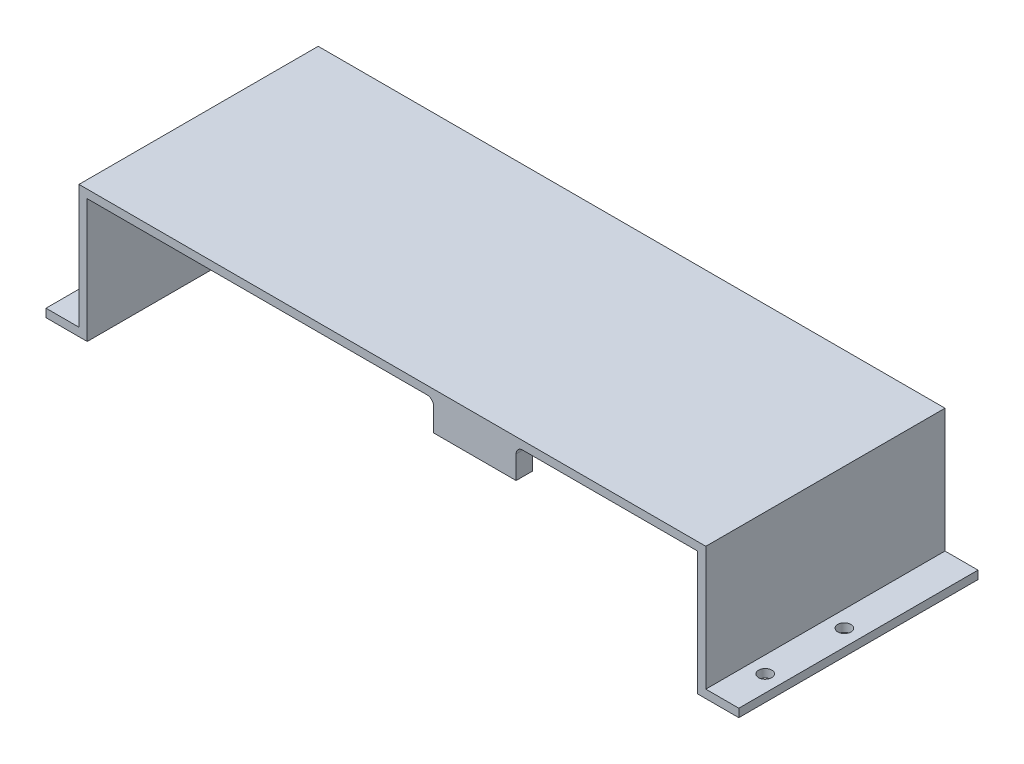
SolidWorks part; units mm, degrees
other "Markup1"
sketch "Sketch8" plane through (104.775, 3.175, 31.75) normal (0.0545, 0.0227, 0.9983) x (-0.9792, -0.1942, 0.0579)
ref_plane "Front Plane" through (0, 0, 0) normal (0, 0, 1) x (1, 0, 0)
ref_plane "Top Plane" through (0, 0, 0) normal (0, 1, 0) x (1, 0, 0)
ref_plane "Right Plane" through (0, 0, 0) normal (1, 0, 0) x (0, 0, -1)
sketch "Sketch1" plane through (0, 0, 0) normal (0, 1, 0) x (1, 0, 0)
  line L1 (-117.475, 46.0375) -> (117.475, 46.0375)
  line L2 (-117.475, 46.0375) -> (-117.475, -46.0375)
  line L3 (-117.475, -46.0375) -> (117.475, -46.0375)
  line L4 (117.475, 46.0375) -> (117.475, -46.0375)
  line L5 (-117.475, 46.0375) -> (117.475, -46.0375) construction
  line L6 (-117.475, -46.0375) -> (117.475, 46.0375) construction
  point P0 (0, 0)
  dimension "D1" = 234.95
  dimension "D2" = 92.075
extrude "Boss-Extrude1" add sketch "Sketch1" along normal blind 3.175
sketch "Sketch3" plane through (0, 3.175, 0) normal (0, 1, 0) x (1, 0, 0)
  line L0 (-117.475, -46.0375) -> (117.475, -46.0375) construction
  line L1 (-117.475, 46.0375) -> (-120.65, 46.0375)
  line L2 (-117.475, 46.0375) -> (-117.475, -46.0375)
  line L3 (-117.475, -46.0375) -> (-120.65, -46.0375)
  line L4 (-120.65, 46.0375) -> (-120.65, -46.0375)
  line L5 (0, -55) -> (0, 55) construction
  line L6 (117.475, -46.0375) -> (120.65, -46.0375)
  line L7 (120.65, 46.0375) -> (120.65, -46.0375)
  line L8 (117.475, 46.0375) -> (120.65, 46.0375)
  line L9 (117.475, 46.0375) -> (117.475, -46.0375)
  dimension "D1" = 3.175
extrude "Boss-Extrude2" add sketch "Sketch3" against normal blind 50.8
sketch "Sketch4" plane through (120.65, 0, 0) normal (1, 0, 0) x (0, 0, -1)
  line L0 (46.0375, -47.625) -> (46.0375, 3.175) construction
  line L1 (-46.0375, -47.625) -> (46.0375, -47.625)
  line L2 (-46.0375, -47.625) -> (-46.0375, -44.45)
  line L3 (-46.0375, -44.45) -> (46.0375, -44.45)
  line L4 (46.0375, -47.625) -> (46.0375, -44.45)
  dimension "D1" = 3.175
extrude "Boss-Extrude3" add sketch "Sketch4" along normal blind 12.7
sketch "Sketch5" plane through (0, -47.625, 0) normal (0, -1, 0) x (1, 0, 0)
  line L2 (117.475, 46.0375) -> (133.35, 46.0375) construction
  line L3 (117.475, 0) -> (133.35, 0) construction
  line L4 (117.475, 46.0375) -> (117.475, -46.0375) construction
  line L5 (133.35, 46.0375) -> (133.35, -46.0375) construction
  circle A0 centre (127, -0.9525) radius 2.54
  circle A1 centre (127, 29.5275) radius 2.54
  dimension "D1" = 5.08
  dimension "D5" = 5.08
  dimension "D2" = 6.35
  dimension "D3" = 16.51
  dimension "D4" = 30.48
  dimension "D6" = 6.35
extrude "Cut-Extrude1" cut sketch "Sketch5" against normal blind 12.7
mirror "Mirror1" about plane through (0, 0, 0) normal (1, 0, 0) of "Boss-Extrude3", "Cut-Extrude1"
sketch "Sketch6" plane through (0, 0, 46.0375) normal (0, 0, 1) x (1, 0, 0)
  line L14 (-117.475, 0) -> (117.475, 0) construction
  line L15 (15.875, 0) -> (47.625, 0)
  line L16 (15.875, 0) -> (15.875, -11.43)
  line L17 (15.875, -11.43) -> (47.625, -11.43)
  line L18 (47.625, 0) -> (47.625, -11.43)
  line L19 (-117.475, -47.625) -> (-117.475, 0) construction
  dimension "D1" = 11.43
  dimension "D2" = 31.75
  dimension "D3" = 165.1
extrude "Boss-Extrude4" add sketch "Sketch6" against normal blind 6.35
fillet "Fillet1" radius 2.54 2 edges at (47.625, 0, 42.8625) (15.875, 0, 42.8625)
